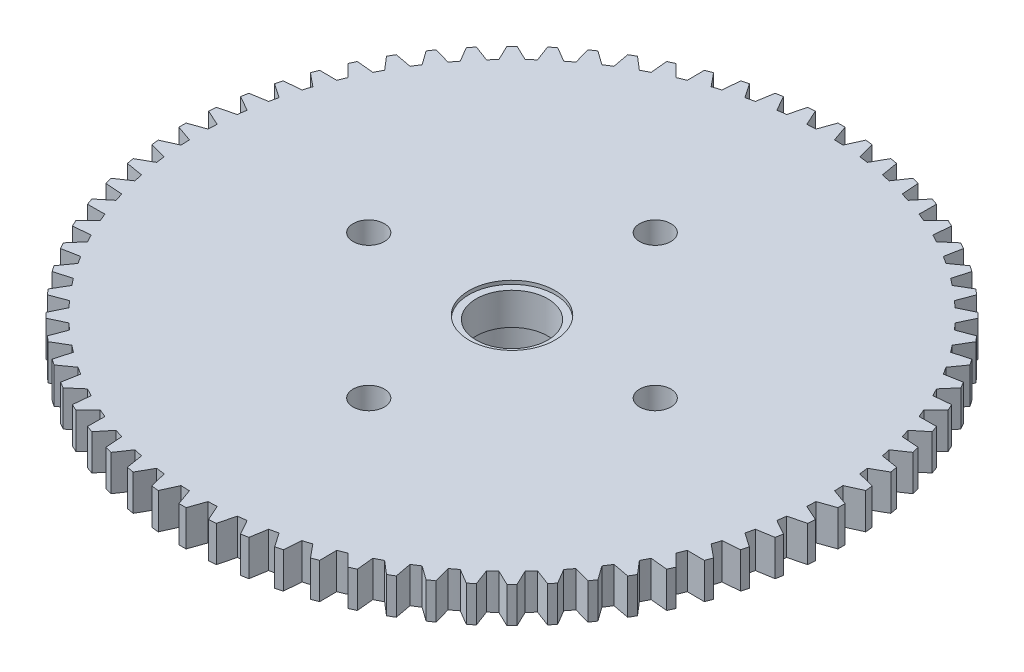
SolidWorks part; units mm, degrees
material "ABS"
ref_plane "Front" through (0, 0, 0) normal (0, 0, 1) x (1, 0, 0)
ref_plane "Top" through (0, 0, 0) normal (0, 1, 0) x (1, 0, 0)
ref_plane "Right" through (0, 0, 0) normal (1, 0, 0) x (0, 0, -1)
sketch "Sketch2" plane through (0, 0, 0) normal (0, 1, 0) x (1, 0, 0)
  circle A0 centre (0, 0) radius 21.875
  circle A1 centre (0, 0) radius 2.5
  dimension "D1" = 43.75
  dimension "D2" = 5
extrude "Boss-Extrude1" add sketch "Sketch2" along normal blind 2.5
ref_plane "Plane1" through (0, 0, 0) normal (0, 1, 0) x (1, 0, 0)
sketch "Sketch3" plane through (0, 0, 0) normal (0, 1, 0) x (1, 0, 0)
  line L0 (0, 21.875) -> (0, -21.875) construction
  line L1 (-21.875, 0) -> (21.875, 0) construction
  line L3 (0, 21.875) -> (0, 23) construction
  line L4 (-0.65, 21.8653) -> (-0.25, 23)
  line L5 (-0.25, 23) -> (0.25, 23)
  line L6 (0.65, 21.8653) -> (0.25, 23)
  circle A0 centre (0, 0) radius 21.875 construction
  arc A1 (-21.875, 0) -> (21.875, 0) centre (0, 0) ccw
  arc A2 (0.65, 21.8653) -> (-0.65, 21.8653) centre (0, 0) ccw
  dimension "D1" = 1.3
  dimension "D2" = 0.25
  dimension "D3" = 23
extrude "Boss-Extrude2" add sketch "Sketch3" along normal blind 2.5 contours L6 L5 L4 A2
pattern_circular "CirPattern1" count 72 over 360 about axis through (0, 2.5, 0) along (0, 1, 0) of "Boss-Extrude2"
sketch "Sketch4" plane through (0, 2.5, 0) normal (0, 1, 0) x (1, 0, 0)
  circle A0 centre (0, 0) radius 3
  circle A1 centre (0, 0) radius 2.5
  circle A2 centre (0, 0) radius 2.5 construction
  dimension "D1" = 0.5
extrude "Cut-Extrude1" cut sketch "Sketch4" against normal blind 0.25
ref_plane "Plane2" through (0, 2.5, 0) normal (0, 1, 0) x (1, 0, 0)
sketch "Sketch5" plane through (0, 2.5, 0) normal (0, 1, 0) x (1, 0, 0)
  line L0 (-34.259, 0) -> (34.259, 0) construction
  line L1 (0, -34.259) -> (0, 34.259) construction
  circle A0 centre (0, 10) radius 1.09
  point P6 (0, 0)
  dimension "D1" = 10
  dimension "D2" = 2.18
extrude "Cut-Extrude2" cut sketch "Sketch5" against normal up to surface (2.5 mm away) up to face at (0, 0, 0)
pattern_circular "CirPattern2" count 4 over 360 about axis through (0, 2.25, 0) along (0, 1, 0) of "Cut-Extrude2"
sketch "Sketch6" plane through (0, 0, 0) normal (0, -1, 0) x (-1, 0, 0)
  circle A0 centre (0, 0) radius 3.15
  circle A1 centre (0, 0) radius 2.8
  dimension "D1" = 6.3
  dimension "D2" = 5.6
extrude "Boss-Extrude3" add sketch "Sketch6" along normal blind 3
